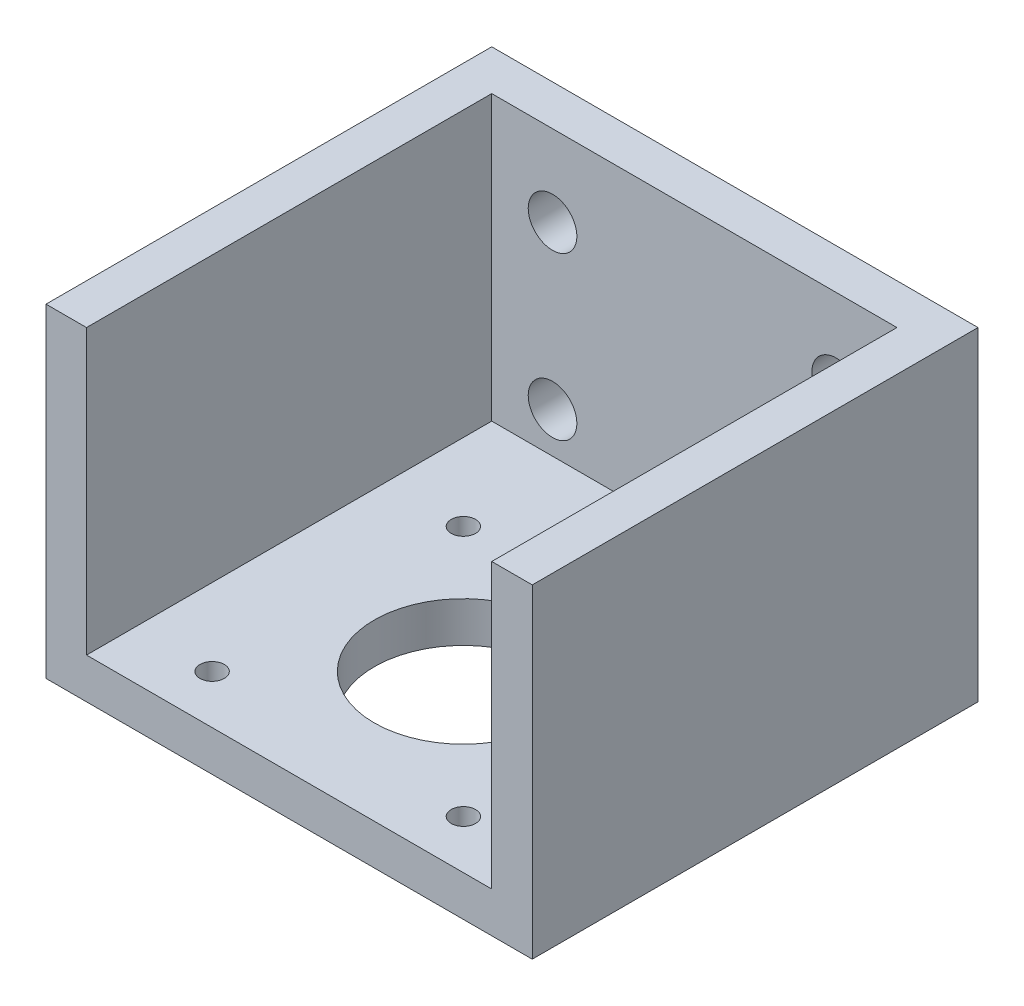
SolidWorks part; units mm, degrees
ref_plane "Спереди" through (0, 0, 0) normal (0, 0, 1) x (1, 0, 0)
ref_plane "Сверху" through (0, 0, 0) normal (0, 1, 0) x (1, 0, 0)
ref_plane "Справа" through (0, 0, 0) normal (1, 0, 0) x (0, 0, -1)
sketch "Эскиз1" plane through (0, 0, 0) normal (0, 1, 0) x (1, 0, 0)
  line L0 (30, 55) -> (30, 0) construction
  line L1 (0, 0) -> (60, 0)
  line L2 (0, 0) -> (0, 55)
  line L3 (0, 55) -> (60, 55)
  line L4 (60, 0) -> (60, 55)
  line L5 (19, 21.5) -> (41, 21.5) construction
  circle A0 centre (30, 21.5) radius 11
  circle A1 centre (14.5, 37) radius 1.5
  circle A2 centre (45.5, 37) radius 1.5
  circle A3 centre (45.5, 6) radius 1.5
  circle A4 centre (14.5, 6) radius 1.5
  point P17 (0, 0)
  point P18 (0, 0)
  dimension "D5" = 3
  dimension "D7" = 22
  dimension "D1" = 55
  dimension "D2" = 60
  dimension "D3" = 31
  dimension "D4" = 31
  dimension "D6" = 21.5
extrude "Бобышка-Вытянуть1" add sketch "Эскиз1" along normal blind 5
sketch "Эскиз3" plane through (0, 5, 0) normal (0, 1, 0) x (1, 0, 0)
  line L0 (5, 50) -> (55, 50)
  line L1 (55, 50) -> (55, 0)
  line L2 (0, 0) -> (60, 0) construction
  line L3 (55, 0) -> (60, 0)
  line L4 (60, 0) -> (60, 55)
  line L5 (60, 55) -> (0, 55)
  line L6 (0, 55) -> (0, 0)
  line L7 (0, 0) -> (5, 0)
  line L8 (5, 0) -> (5, 50)
  dimension "D1" = 5
  dimension "D2" = 5
  dimension "D3" = 5
  dimension "D4" = 50
extrude "Бобышка-Вытянуть2" add sketch "Эскиз3" along normal blind 35
sketch "Эскиз4" plane through (0, 0, -55) normal (0, 0, -1) x (-1, 0, 0)
  line L0 (-30, 0) -> (-30, 40) construction
  line L1 (-60, 0) -> (0, 0) construction
  line L2 (-60, 40) -> (0, 40) construction
  line L3 (0, 10) -> (-60, 10) construction
  line L4 (0, 40) -> (0, 0) construction
  line L5 (-60, 40) -> (-60, 0) construction
  line L6 (-60, 30) -> (0, 30) construction
  circle A0 centre (-12.5, 10) radius 3
  circle A1 centre (-12.5, 30) radius 3
  circle A2 centre (-47.5, 30) radius 3
  circle A3 centre (-47.5, 10) radius 3
  point P22 (0, 0)
  point P23 (0, 0)
  dimension "D3" = 6
  dimension "D1" = 10
  dimension "D2" = 10
  dimension "D4" = 35
  dimension "D5" = 35
extrude "Вырез-Вытянуть1" cut sketch "Эскиз4" against normal up to surface (5 mm away) up to face at (30, 22.5, -50)
